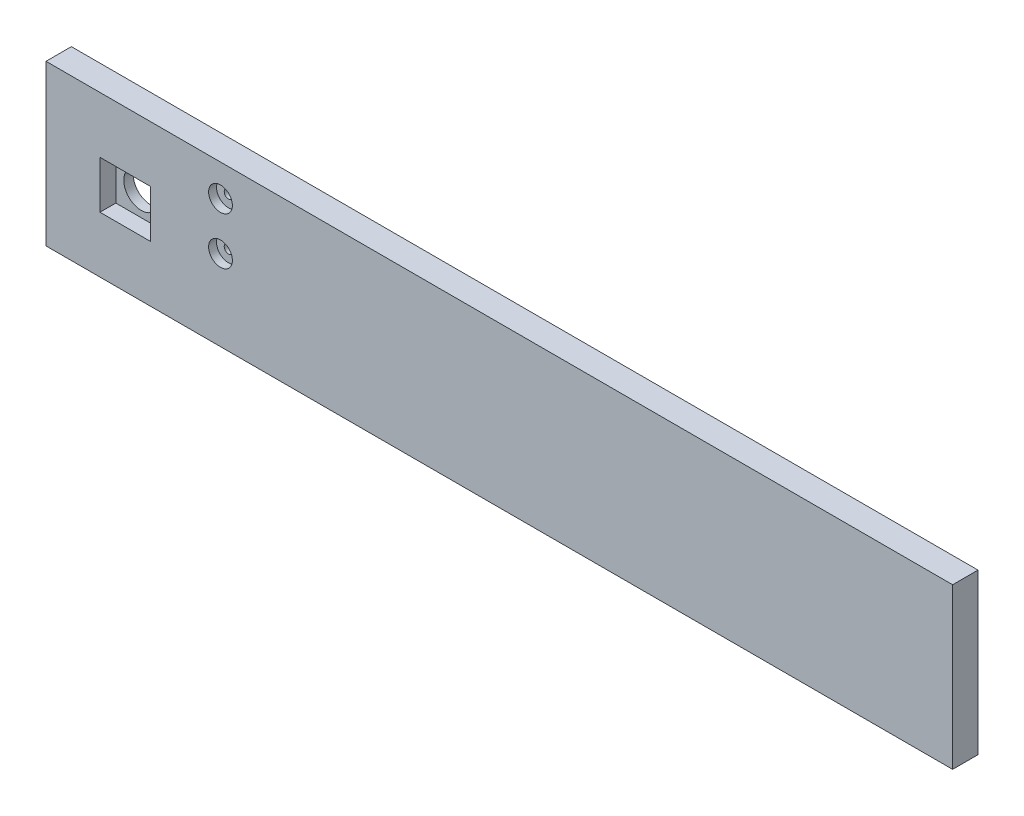
SolidWorks part; units mm, degrees
ref_plane "Front Plane" through (0, 0, 0) normal (0, 0, 1) x (1, 0, 0)
ref_plane "Top Plane" through (0, 0, 0) normal (0, 1, 0) x (1, 0, 0)
ref_plane "Right Plane" through (0, 0, 0) normal (1, 0, 0) x (0, 0, -1)
sketch "Sketch1" plane through (0, 0, 0) normal (0, 0, 1) x (1, 0, 0)
  line L1 (0, 0) -> (571.5, 0)
  line L2 (0, 0) -> (0, 100.8)
  line L3 (0, 100.8) -> (571.5, 100.8)
  line L4 (571.5, 0) -> (571.5, 100.8)
  dimension "D1" = 100.8
  dimension "D2" = 571.5
extrude "Boss-Extrude1" add sketch "Sketch1" along normal mid plane 16
sketch "Sketch9" plane through (0, 0, 8) normal (0, 0, 1) x (1, 0, 0)
  line L0 (571.5, 100.8) -> (0, 100.8) construction
  line L1 (0, 100.8) -> (0, 0) construction
  circle A0 centre (50, 50.4) radius 11
  circle A1 centre (110, 80.8) radius 2.65
  circle A3 centre (110, 50.8) radius 2.65
  dimension "D1" = 22
  dimension "D2" = 50.4
  dimension "D3" = 50
  dimension "D4" = 5.3
  dimension "D5" = 5.3
  dimension "D6" = 20
  dimension "D7" = 30
  dimension "D8" = 60
extrude "Cut-Extrude1" cut sketch "Sketch9" against normal through all and the other way through all
sketch "Sketch10" plane through (0, 0, 8) normal (0, 0, 1) x (1, 0, 0)
  line L1 (34, 65.4) -> (66, 65.4)
  line L2 (34, 65.4) -> (34, 35.4)
  line L3 (34, 35.4) -> (66, 35.4)
  line L4 (66, 65.4) -> (66, 35.4)
  line L5 (34, 65.4) -> (66, 35.4) construction
  line L6 (34, 35.4) -> (66, 65.4) construction
  point P0 (50, 50.4)
  dimension "D1" = 32
  dimension "D2" = 30
extrude "Cut-Extrude2" cut sketch "Sketch10" against normal blind 10
sketch "Sketch11" plane through (0, 0, 8) normal (0, 0, 1) x (1, 0, 0)
  circle A0 centre (110, 80.8) radius 7.5
  circle A1 centre (110, 50.8) radius 7.5
  dimension "D1" = 15
  dimension "D2" = 15
extrude "Cut-Extrude3" cut sketch "Sketch11" against normal blind 5
extrude "Cut-Extrude4" cut sketch "Sketch11<2>" along normal blind 5 from surface starting at face at (61, 50.4, -8)
sketch "Sketch11<2>" plane through (0, 0, 8) normal (0, 0, 1) x (1, 0, 0) same geometry as "Sketch11"
